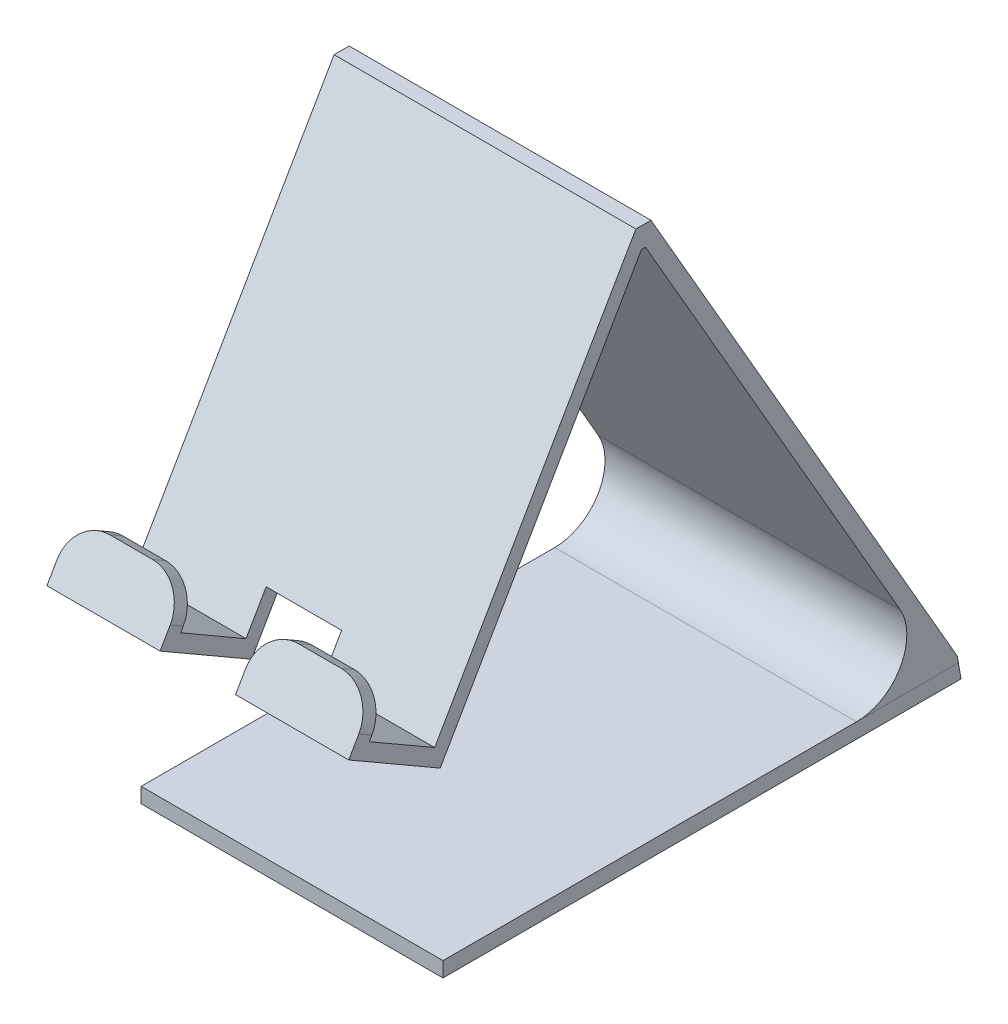
SolidWorks part; units mm, degrees
ref_plane "Front Plane" through (0, 0, 0) normal (0, 0, 1) x (1, 0, 0)
ref_plane "Top Plane" through (0, 0, 0) normal (0, 1, 0) x (1, 0, 0)
ref_plane "Right Plane" through (0, 0, 0) normal (1, 0, 0) x (0, 0, -1)
sketch "Sketch1" plane through (0, 0, 0) normal (0, 1, 0) x (1, 0, 0)
  line L1 (-30, 51.5) -> (30, 51.5)
  line L2 (-30, 51.5) -> (-30, -51.5)
  line L3 (-30, -51.5) -> (30, -51.5)
  line L4 (30, 51.5) -> (30, -51.5)
  line L5 (-30, 51.5) -> (30, -51.5) construction
  line L6 (-30, -51.5) -> (30, 51.5) construction
  point P0 (0, 0)
  dimension "D1" = 60
  dimension "D2" = 103
extrude "Boss-Extrude1" add sketch "Sketch1" along normal blind 3
sketch "Sketch3" plane through (30, 0, 0) normal (1, 0, 0) x (0, 0, -1)
  line L0 (51.5, 0) -> (51.5, 107) construction
  line L1 (51.5, 3) -> (-8.6517, 107.1859)
  line L2 (-51.5, 3) -> (51.5, 3) construction
  line L4 (-11.2498, 105.6859) -> (-8.6517, 107.1859)
  line L6 (30.7154, 3) -> (48.0359, 3)
  line L7 (39.3756, 18) -> (-11.2498, 105.6859)
  line L8 (48.0359, 3) -> (51.5, 3)
  arc A0 (30.7154, 3) -> (39.3756, 18) centre (30.7154, 13) ccw
  dimension "D4" = 20
  dimension "D1" = 107
  dimension "D2" = 60
base flange "Base-Flange1" sketch "Sketch3" thickness 60 reverse thickness direction no parameters "D1"=2.5
sketch "Sketch8" plane through (30, 0, 0) normal (1, 0, 0) x (0, 0, -1)
  line L0 (-14.6517, 107.1859) -> (-13.1517, 109.7839)
  line L1 (-14.6517, 107.1859) -> (-53.1517, 40.5019)
  line L2 (-11.2498, 105.6859) -> (39.3756, 18) construction
  line L3 (-12.0537, 105.6859) -> (-52.0537, 36.4038)
  line L4 (-8.6517, 107.1859) -> (-10.1517, 109.7839)
  line L5 (-10.1517, 109.7839) -> (-13.1517, 109.7839)
  line L6 (-12.0537, 105.6859) -> (-11.2498, 105.6859)
  line L7 (-52.0537, 36.4038) -> (-54.6517, 37.9038)
  line L8 (-54.6517, 37.9038) -> (-67.6421, 45.4038)
  line L9 (-14.6517, 107.1859) -> (-54.6517, 37.9038) construction
  line L10 (-68.7402, 49.5019) -> (-70.2402, 46.9038)
  line L11 (-70.2402, 46.9038) -> (-67.6421, 45.4038)
  line L12 (-53.1517, 40.5019) -> (-66.1421, 48.0019)
  line L13 (-68.7402, 49.5019) -> (-66.1421, 48.0019)
  line L14 (-8.6517, 107.1859) -> (-11.2498, 105.6859)
  dimension "D1" = 3
  dimension "D2" = 80
  dimension "D3" = 60
  dimension "D5" = 15
  dimension "D4" = 3
  dimension "D8" = 3
base flange "Tab2" sketch "Sketch8" thickness 60 reverse thickness direction no parameters "D1"=2.5
sketch "Sketch15" plane through (0, 33.1409, 57.4016) normal (0, 0.5, 0.866) x (1, 0, 0)
  line L0 (0, 5.4998) -> (0, 8.1735) construction
  line L1 (-30, 5.4998) -> (30, 5.4998) construction
  line L2 (7.5, 5.4998) -> (-7.5, 5.4998)
  line L3 (-7.5, 16.4998) -> (7.5, 16.4998)
  line L4 (-7.5, 16.4998) -> (-7.5, 5.4998)
  line L6 (7.5, 16.4998) -> (7.5, 5.4998)
  line L7 (-7.5, 16.4998) -> (1.0376, 5.4998) construction
  line L8 (-1.0376, 5.4998) -> (7.5, 16.4998) construction
  point P5 (0, 6.8367)
  dimension "D1" = 15
  dimension "D2" = 11
extrude "Cut-Extrude2" cut sketch "Sketch15" against normal mid plane 58
sketch "Sketch16" plane through (0, 42.1409, 72.9901) normal (0, 0.5, 0.866) x (1, 0, 0)
  line L0 (-30, 8.4998) -> (-30, 16.4998)
  line L1 (-30, 88.4998) -> (-30, 8.4998) construction
  line L2 (-30, 16.4998) -> (-7.5, 16.4998)
  line L3 (-7.5, 16.4998) -> (-7.5, 8.4998)
  line L4 (-7.5, 8.4998) -> (-30, 8.4998)
  line L5 (0, 0) -> (0, 16.4998) construction
  line L6 (7.5, 16.4998) -> (-7.5, 16.4998) construction
  line L7 (7.5, 16.4998) -> (7.5, 8.4998)
  line L8 (30, 16.4998) -> (7.5, 16.4998)
  line L9 (30, 8.4998) -> (30, 16.4998)
  line L10 (7.5, 8.4998) -> (30, 8.4998)
extrude "Boss-Extrude2" add sketch "Sketch16" against normal blind 3
fillet "Fillet1" radius 7 4 edges at (30, 55.6801, 63.4412) (7.5, 55.6801, 63.4412) (-7.5, 55.6801, 63.4412) (-30, 55.6801, 63.4412)
sketch "Sketch17" plane through (30, 0, 0) normal (1, 0, 0) x (0, 0, -1)
  line L0 (51.5, 0) -> (50.7384, 4.3191)
  line L1 (-51.5, 0) -> (51.5, 0) construction
  line L2 (50.7384, 4.3191) -> (51.5, 3)
  line L3 (51.5, 3) -> (-10.1517, 109.7839) construction
  line L4 (51.5, 3) -> (51.5, 0)
  dimension "D1" = 80
extrude "Cut-Extrude3" cut sketch "Sketch17" against normal blind 90
sketch "Bend-Lines1" [suppressed] plane through (0, 0, 0) normal (0, 1, 0) x (1, 0, 0)
sketch "Bounding-Box1" [suppressed] plane through (0, 0, 0) normal (0, 1, 0) x (1, 0, 0)
sheet metal parameters "Sheet-Metal2" thickness 60 parameters "D1"=2.5
flat pattern "Flat-Pattern2" [suppressed]
sketch "Bend-Lines2" plane through (0, 0, 0) normal (0, 1, 0) x (1, 0, 0)
sketch3d "Bounding-Box2" [suppressed]
  line L0 (5.1962, -19, 0) -> (-54.9556, 85.1859, 0) construction
  line L1 (20.7846, -10, 0) -> (-39.3671, 94.1859, 0) construction
  line L2 (5.1962, -19, 0) -> (20.7846, -10, 0) construction
  line L3 (-54.9556, 85.1859, 0) -> (-39.3671, 94.1859, 0) construction
sheet metal parameters "Sheet-Metal4" thickness 60 parameters "D1"=2.5
flat pattern "Flat-Pattern4"
sketch "Bend-Lines4" plane through (0, 0, 0) normal (0, 1, 0) x (1, 0, 0)
sketch3d "Bounding-Box4" [suppressed]
  line L0 (-51.5096, -51.7391, 0) -> (-113.9114, 56.3439, 0) construction
  line L1 (20.7846, -10, 0) -> (-41.6171, 98.083, 0) construction
  line L2 (-51.5096, -51.7391, 0) -> (20.7846, -10, 0) construction
  line L3 (-113.9114, 56.3439, 0) -> (-41.6171, 98.083, 0) construction
sheet metal parameters "Sheet-Metal6" thickness 60 parameters "D1"=2.5
flat pattern "Flat-Pattern4"
sketch "Bend-Lines4" plane through (0, 0, 0) normal (0, 1, 0) x (1, 0, 0)
sketch3d "Bounding-Box4" [suppressed]
  line L0 (-51.5096, -51.7391, 0) -> (-113.9114, 56.3439, 0) construction
  line L1 (20.7846, -10, 0) -> (-41.6171, 98.083, 0) construction
  line L2 (-51.5096, -51.7391, 0) -> (20.7846, -10, 0) construction
  line L3 (-113.9114, 56.3439, 0) -> (-41.6171, 98.083, 0) construction
sheet metal parameters "Sheet-Metal7" thickness 60 parameters "D1"=2.5
flat pattern "Flat-Pattern4"
sketch "Bend-Lines4" plane through (0, 0, 0) normal (0, 1, 0) x (1, 0, 0)
sketch3d "Bounding-Box4" [suppressed]
  line L0 (20.7846, -10, 0) -> (-100.9556, -10, 0) construction
  line L1 (20.7846, 96.7839, 0) -> (-100.9556, 96.7839, 0) construction
  line L2 (20.7846, -10, 0) -> (20.7846, 96.7839, 0) construction
  line L3 (-100.9556, -10, 0) -> (-100.9556, 96.7839, 0) construction
sheet metal parameters "Sheet-Metal9" thickness 60 parameters "D1"=2.5
flat pattern "Flat-Pattern4"
sketch "Bend-Lines4" plane through (0, 0, 0) normal (0, 1, 0) x (1, 0, 0)
sketch3d "Bounding-Box4" [suppressed]
  line L0 (20.2556, -10, 0) -> (-100.9556, -10, 0) construction
  line L1 (20.2556, 96.7839, 0) -> (-100.9556, 96.7839, 0) construction
  line L2 (20.2556, -10, 0) -> (20.2556, 96.7839, 0) construction
  line L3 (-100.9556, -10, 0) -> (-100.9556, 96.7839, 0) construction
